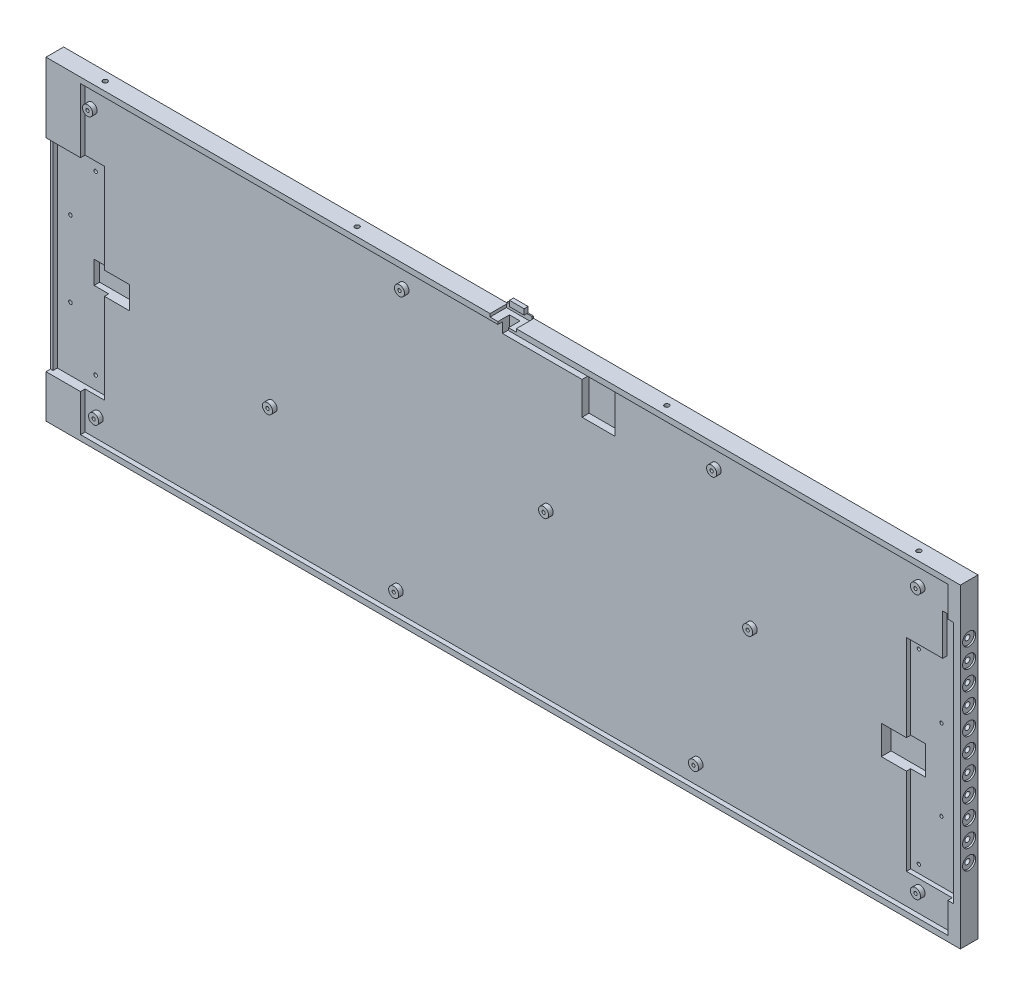
SolidWorks part; units mm, degrees
ref_plane "前视基准面" through (0, 0, 0) normal (0, 0, 1) x (1, 0, 0)
ref_plane "上视基准面" through (0, 0, 0) normal (0, 1, 0) x (1, 0, 0)
ref_plane "右视基准面" through (0, 0, 0) normal (1, 0, 0) x (0, 0, -1)
other "Configuration Table"
sketch "草图1" plane through (0, 0, 0) normal (0, 0, 1) x (1, 0, 0)
  line L1 (0, 0) -> (348.235, 0)
  line L2 (0, 0) -> (0, -124.714)
  line L3 (0, -124.714) -> (348.235, -124.714)
  line L4 (348.235, 0) -> (348.235, -124.714)
  dimension "D1" = 348.235
  dimension "D2" = 124.714
extrude "凸台-拉伸1" add sketch "草图1" along normal blind 7
sketch "草图2" plane through (0, 0, 7) normal (0, 0, 1) x (1, 0, 0)
  line L0 (348.235, 0) -> (0, 0) construction
  line L1 (2, -2) -> (346.235, -2)
  line L2 (2, -2) -> (2, -122.714)
  line L3 (2, -122.714) -> (346.235, -122.714)
  line L4 (346.235, -2) -> (346.235, -122.714)
  line L5 (348.235, -124.714) -> (348.235, 0) construction
  line L6 (0, -124.714) -> (348.235, -124.714) construction
  line L7 (0, 0) -> (0, -124.714) construction
  dimension "D1" = 2
  dimension "D2" = 2
  dimension "D3" = 2
  dimension "D4" = 2
extrude "切除-拉伸1" cut sketch "草图2" against normal blind 1.8
sketch "草图3" plane through (0, 0, 5.2) normal (0, 0, 1) x (1, 0, 0)
  circle A0 centre (4.8, -9.9) radius 2
  circle A1 centre (4.8, -9.9) radius 0.65
  circle A2 centre (7.2, -114.7) radius 2
  circle A3 centre (7.2, -114.7) radius 0.65
  circle A4 centre (76.2, -76.6) radius 2
  circle A5 centre (76.2, -76.6) radius 0.65
  circle A6 centre (128.6, -9.9) radius 2
  circle A7 centre (128.6, -9.9) radius 0.65
  circle A8 centre (126.3, -114.7) radius 2
  circle A9 centre (126.3, -114.7) radius 0.65
  circle A10 centre (185.8, -57.5) radius 2
  circle A11 centre (185.8, -57.5) radius 0.65
  circle A12 centre (252.5, -9.9) radius 2
  circle A13 centre (252.5, -9.9) radius 0.65
  circle A14 centre (245.3, -114.7) radius 2
  circle A15 centre (245.3, -114.7) radius 0.65
  circle A16 centre (333.4, -9.9) radius 2
  circle A17 centre (333.4, -9.9) radius 0.65
  circle A18 centre (333.4, -114.7) radius 2
  circle A19 centre (333.4, -114.7) radius 0.65
  circle A20 centre (266.8, -57.5) radius 2
  circle A21 centre (266.8, -57.5) radius 0.65
  dimension "D1" = 4
  dimension "D2" = 1.3
extrude "凸台-拉伸2" add sketch "草图3" along normal up to surface (1.8 mm away) up to face at (174.1175, -62.357, 7)
sketch "草图4" plane through (0, 0, 5.2) normal (0, 0, 1) x (1, 0, 0)
  line L0 (0, 0) -> (0, -124.714) construction
  line L1 (0, -27.514) -> (9.7, -27.514)
  line L2 (0, -27.514) -> (0, -107.914)
  line L3 (0, -107.914) -> (9.7, -107.914)
  line L4 (9.7, -27.514) -> (9.7, -107.914)
  line L5 (0, -124.714) -> (348.235, -124.714) construction
  dimension "D1" = 80.4
  dimension "D2" = 9.7
  dimension "D3" = 16.8
extrude "切除-拉伸2" cut sketch "草图4" against normal blind 1.7 and the other way through all contours L4 L3 L2 L1
sketch "草图6" plane through (0, 0, 5.2) normal (0, 0, 1) x (1, 0, 0)
  line L5 (3.9, -67.714) -> (9.7, -67.714) construction
  line L6 (3.9, -63.214) -> (19.7, -63.214)
  line L7 (3.9, -63.214) -> (3.9, -72.214)
  line L8 (3.9, -72.214) -> (19.7, -72.214)
  line L9 (19.7, -63.214) -> (19.7, -72.214)
  line L10 (9.7, -27.514) -> (9.7, -107.914) construction
  dimension "D1" = 9
  dimension "D2" = 5.8
  dimension "D3" = 10
extrude "切除-拉伸3" cut sketch "草图6" against normal offset from surface (3.9 mm away) 1.3 up to face at (174.1175, -62.357, 0)
sketch "草图7" plane through (0, 0, 0) normal (-1, 0, 0) x (0, 0, 1)
  line L1 (0, 0) -> (7, 0)
  line L2 (0, 0) -> (0, -27.514)
  line L3 (0, -27.514) -> (7, -27.514)
  line L4 (7, 0) -> (7, -27.514)
  line L5 (7, -107.914) -> (0, -107.914)
  line L6 (7, -107.914) -> (7, -124.714)
  line L7 (7, -124.714) -> (0, -124.714)
  line L8 (0, -107.914) -> (0, -124.714)
  line L9 (0, -107.914) -> (3.5, -107.914)
  line L10 (0, -107.914) -> (0, -27.514)
  line L11 (0, -27.514) -> (3.5, -27.514)
  line L12 (3.5, -107.914) -> (3.5, -27.514)
  line M1 (3.5, -107.914) -> (3.5, -27.514)
  line M2 (3.5, -27.514) -> (7, -27.514)
  line M3 (7, -27.514) -> (7, 0)
  line M4 (7, 0) -> (0, 0)
  line M5 (0, 0) -> (0, -124.714)
  line M6 (0, -124.714) -> (7, -124.714)
  line M7 (7, -124.714) -> (7, -107.914)
  line M8 (7, -107.914) -> (3.5, -107.914)
extrude "凸台-拉伸3" add sketch "草图7" along normal blind 11.7 contours L5 M8 M5 M6 M7 | L5 L3 M1 M5 | L3 M5 M2 M3 M4 region at (0, -13.757, 3.5) region at (0, -67.714, 1.75) region at (0, -116.314, 3.5)
sketch "草图8" plane through (0, 0, 3.5) normal (0, 0, 1) x (1, 0, 0)
  circle A0 centre (-5.5, -82.714) radius 0.7
  circle A1 centre (4.5, -102.714) radius 0.7
  circle A2 centre (-5.5, -52.714) radius 0.7
  circle A3 centre (4.5, -32.714) radius 0.7
  dimension "D1" = 1.4
extrude "切除-拉伸4" cut sketch "草图8" against normal blind 3
sketch "草图9" plane through (0, 0, 3.5) normal (0, 0, 1) x (1, 0, 0)
  line L0 (-11.7, -107.914) -> (2, -107.914) construction
  line L1 (-11.7, -27.514) -> (-10.7, -27.514)
  line L2 (-11.7, -27.514) -> (-11.7, -107.914)
  line L3 (-11.7, -107.914) -> (-10.7, -107.914)
  line L4 (-10.7, -27.514) -> (-10.7, -107.914)
  dimension "D1" = 1
extrude "凸台-拉伸4" add sketch "草图9" along normal up to surface (1.7 mm away) up to face at (64.8892, -65.9283, 5.2)
sketch "草图10" plane through (0, 0, 5.2) normal (0, 0, 1) x (1, 0, 0)
  line L1 (328.035, -30.314) -> (348.235, -30.314)
  line L2 (328.035, -30.314) -> (328.035, -110.714)
  line L3 (328.035, -110.714) -> (348.235, -110.714)
  line L4 (348.235, -30.314) -> (348.235, -110.714)
  line L6 (348.235, -124.714) -> (348.235, 0) construction
  line L9 (2, -122.714) -> (346.235, -122.714) construction
  dimension "D1" = 80.4
  dimension "D2" = 20.2
  dimension "D3" = 12
extrude "切除-拉伸5" cut sketch "草图10" against normal blind 1.7 and the other way through all
sketch "草图11" plane through (0, 0, 3.5) normal (0, 0, 1) x (1, 0, 0)
  line L0 (328.035, -70.514) -> (333.835, -70.514) construction
  line L1 (318.035, -64.764) -> (333.835, -64.764)
  line L2 (318.035, -64.764) -> (318.035, -76.264)
  line L3 (318.035, -76.264) -> (333.835, -76.264)
  line L4 (333.835, -64.764) -> (333.835, -76.264)
  line L5 (328.035, -110.714) -> (328.035, -30.314) construction
  dimension "D1" = 11.5
  dimension "D2" = 5.8
  dimension "D3" = 10
extrude "切除-拉伸6" cut sketch "草图11" against normal blind 2.2 and the other way through all
sketch "草图12" plane through (0, 0, 3.5) normal (0, 0, 1) x (1, 0, 0)
  circle A3 centre (331.235, -107.514) radius 0.65
  circle A4 centre (340.235, -86.514) radius 0.65
  circle A5 centre (340.235, -54.514) radius 0.65
  circle A6 centre (331.235, -33.514) radius 0.65
  dimension "D1" = 1.3
extrude "切除-拉伸7" cut sketch "草图12" against normal blind 3
sketch "草图13" plane through (0, 0, 0) normal (0, 0, -1) x (-1, 0, 0)
  line L0 (11.7, -124.714) -> (-348.235, -124.714) construction
  line L1 (-348.235, 0) -> (-351.235, 0)
  line L2 (-348.235, 0) -> (-348.235, -124.714)
  line L3 (-348.235, -124.714) -> (-351.235, -124.714)
  line L4 (-351.235, 0) -> (-351.235, -124.714)
  dimension "D1" = 3
extrude "凸台-拉伸5" add sketch "草图13" against normal up to surface (7 mm away) up to face at (171.1925, -14.957, 7)
sketch "草图14" plane through (0, 0, 5.2) normal (0, 0, 1) x (1, 0, 0)
  line L0 (346.235, -2) -> (2, -2) construction
  line L1 (342.435, -14) -> (348.435, -14)
  line L2 (342.435, -14) -> (342.435, -110.714)
  line L3 (342.435, -110.714) -> (348.435, -110.714)
  line L4 (348.435, -14) -> (348.435, -110.714)
  line L5 (346.235, -110.714) -> (328.035, -110.714) construction
  line L6 (351.235, 0) -> (351.235, -124.714) construction
  dimension "D1" = 12
  dimension "D2" = 6
  dimension "D3" = 2.8
extrude "切除-拉伸8" cut sketch "草图14" against normal up to surface (1.7 mm away) and the other way blind 3 up to face at (340.885, -86.514, 3.5)
sketch "草图15" plane through (351.235, 0, 0) normal (1, 0, 0) x (0, 0, -1)
  line L0 (-7, 0) -> (0, 0) construction
  line L1 (-3.5, -20) -> (-3.5, 0)
  line L2 (-3.5, -104.714) -> (-3.5, -124.714)
  line L4 (-7, -124.714) -> (0, -124.714) construction
  circle A0 centre (-3.5, -20) radius 2.6
  circle A12 centre (-3.5, -20) radius 1
  circle A13 centre (-3.5, -27.7013) radius 2.6
  circle A14 centre (-3.5, -27.7013) radius 1
  circle A15 centre (-3.5, -35.4025) radius 2.6
  circle A16 centre (-3.5, -35.4025) radius 1
  circle A17 centre (-3.5, -43.1038) radius 2.6
  circle A18 centre (-3.5, -43.1038) radius 1
  circle A19 centre (-3.5, -50.8051) radius 2.6
  circle A20 centre (-3.5, -50.8051) radius 1
  circle A21 centre (-3.5, -58.5064) radius 2.6
  circle A22 centre (-3.5, -58.5064) radius 1
  circle A23 centre (-3.5, -66.2076) radius 2.6
  circle A24 centre (-3.5, -66.2076) radius 1
  circle A25 centre (-3.5, -73.9089) radius 2.6
  circle A26 centre (-3.5, -73.9089) radius 1
  circle A27 centre (-3.5, -81.6102) radius 2.6
  circle A28 centre (-3.5, -81.6102) radius 1
  circle A29 centre (-3.5, -89.3115) radius 2.6
  circle A30 centre (-3.5, -89.3115) radius 1
  circle A31 centre (-3.5, -97.0127) radius 2.6
  circle A32 centre (-3.5, -97.0127) radius 1
  circle A33 centre (-3.5, -104.714) radius 2.6
  circle A34 centre (-3.5, -104.714) radius 1
  point P5 (-3.5, 0)
  dimension "D2" = 5.2
  dimension "D3" = 2
  dimension "D1" = 20
  dimension "D4" = 12
extrude "切除-拉伸9" cut sketch "草图15" against normal blind 0.7 contours A0 | A13 | A15 | A17 | A19 | A21 | A23 | A25 | A27 | A29 | A31
extrude "切除-拉伸10" cut sketch "草图15<3>" against normal up to surface (2.8 mm away) contours A12 | A14 | A16 | A18 | A20 | A22 | A24 | A26 | A28 | A30 | A32 up to face at (348.435, -62.357, 5.25)
sketch "草图15<3>" plane through (351.235, 0, 0) normal (1, 0, 0) x (0, 0, -1) same geometry as "草图15"
sketch "草图16" plane through (0, 0, 0) normal (0, 1, 0) x (1, 0, 0)
  line L1 (-11.7, 0) -> (351.235, 0)
  line L2 (-11.7, 0) -> (-11.7, -7)
  line L3 (-11.7, -7) -> (351.235, -7)
  line L4 (351.235, 0) -> (351.235, -7)
extrude "凸台-拉伸6" add sketch "草图16" along normal blind 0.2
sketch "草图17" plane through (0, -124.714, 0) normal (0, -1, 0) x (1, 0, 0)
  line L1 (-11.7, 7) -> (351.235, 7)
  line L2 (-11.7, 7) -> (-11.7, 0)
  line L3 (-11.7, 0) -> (351.235, 0)
  line L4 (351.235, 7) -> (351.235, 0)
extrude "凸台-拉伸7" add sketch "草图17" along normal blind 0.2
sketch "草图18" plane through (0, 0.2, 0) normal (0, 1, 0) x (1, 0, 0)
  line L0 (351.235, 0) -> (-11.7, 0) construction
  line L1 (164.5675, -0.5) -> (174.9675, -0.5)
  line L2 (164.5675, -0.5) -> (164.5675, -8.7)
  line L3 (164.5675, -8.7) -> (174.9675, -8.7)
  line L4 (174.9675, -0.5) -> (174.9675, -8.7)
  line L5 (164.5675, -0.5) -> (-11.7, -0.5) construction
  line L6 (-11.7, 0) -> (-11.7, -7) construction
  line L7 (174.9675, -0.5) -> (351.235, -0.5) construction
  line L8 (351.235, -7) -> (351.235, 0) construction
  dimension "D1" = 0.5
  dimension "D2" = 10.4
  dimension "D3" = 8.2
extrude "切除-拉伸11" cut sketch "草图18" against normal blind 1.2
sketch "草图19" plane through (0, 0.2, 0) normal (0, 1, 0) x (1, 0, 0)
  line L0 (174.9675, -7) -> (164.5675, -7) construction
  line L1 (167.6675, -2.4) -> (171.8675, -2.4)
  line L2 (167.6675, -2.4) -> (167.6675, -7)
  line L3 (167.6675, -7) -> (171.8675, -7)
  line L4 (171.8675, -2.4) -> (171.8675, -7)
  line L5 (169.7675, -2.4) -> (169.7675, 0) construction
  line L6 (351.235, 0) -> (-11.7, 0) construction
  line L7 (167.6675, -2.4) -> (-11.7, -2.4) construction
  line L8 (-11.7, 0) -> (-11.7, -7) construction
  line L9 (171.8675, -2.4) -> (351.235, -2.4) construction
  line L10 (351.235, -7) -> (351.235, 0) construction
  dimension "D1" = 2.4
  dimension "D2" = 4.2
extrude "切除-拉伸12" cut sketch "草图19" against normal up to surface (2.2 mm away) up to face at (174.1175, -2, 6.1)
sketch "草图20" plane through (0, 0.2, 0) normal (0, 1, 0) x (1, 0, 0)
  line L1 (174.7675, 0) -> (164.7675, 0)
  line L2 (174.7675, 0) -> (174.7675, -0.5)
  line L3 (174.7675, -0.5) -> (164.7675, -0.5)
  line L4 (164.7675, 0) -> (164.7675, -0.5)
  line L6 (351.235, 0) -> (-11.7, 0) construction
  point P15 (169.7675, 0)
  dimension "D1" = 10
  dimension "D2" = 0.5
extrude "凸台-拉伸8" add sketch "草图20" along normal blind 0.8
sketch "草图21" plane through (0, 1, 0) normal (0, 1, 0) x (1, 0, 0)
  line L0 (164.7675, 0) -> (174.7675, 0) construction
  line L1 (166.8675, 0) -> (172.6675, 0)
  line L2 (166.8675, 0) -> (166.8675, -1.6)
  line L3 (166.8675, -1.6) -> (172.6675, -1.6)
  line L4 (172.6675, 0) -> (172.6675, -1.6)
  point P6 (169.7675, 0)
  dimension "D1" = 5.8
  dimension "D2" = 1.6
extrude "凸台-拉伸9" add sketch "草图21" along normal blind 2.2
sketch "草图22" plane through (0, 0, 5.2) normal (0, 0, 1) x (1, 0, 0)
  line L1 (167.6675, -2) -> (212.2675, -2)
  line L2 (167.6675, -2) -> (167.6675, -6)
  line L3 (167.6675, -6) -> (212.2675, -6)
  line L4 (212.2675, -2) -> (212.2675, -6)
  line L5 (212.2675, -6) -> (199.2675, -6)
  line L6 (212.2675, -6) -> (212.2675, -19)
  line L7 (212.2675, -19) -> (199.2675, -19)
  line L8 (199.2675, -6) -> (199.2675, -19)
  line M20 (346.235, -2) -> (171.8675, -2)
  line M21 (171.8675, -2) -> (167.6675, -2)
  dimension "D1" = 4
  dimension "D2" = 44.6
  dimension "D3" = 13
  dimension "D4" = 13
extrude "切除-拉伸13" cut sketch "草图22" against normal up to surface (2.8 mm away) contours L4 L2 L3 M20 M21 | L3 L8 L7 L6 region at (189.9675, -4, 5.2) region at (205.7675, -12.5, 5.2) up to face at (169.7675, -1.5, 2.4)
sketch "草图23" plane through (0, 0, 0) normal (0, 0, -1) x (-1, 0, 0)
  line L0 (-351.235, 0.2) -> (-351.235, -124.914) construction
  line L1 (11.7, 0.2) -> (11.7, -124.914) construction
  line L2 (-351.235, 0.2) -> (-174.7675, 0.2) construction
  line L3 (11.7, -124.914) -> (-351.235, -124.914) construction
  circle A0 centre (-331.235, -19.8) radius 5.6
  circle A1 centre (-231.235, -19.8) radius 5.6
  circle A2 centre (-108.3, -19.8) radius 5.6
  circle A3 centre (-8.3, -19.8) radius 5.6
  circle A4 centre (-331.235, -104.914) radius 4.1
  circle A5 centre (-231.235, -104.914) radius 4.1
  circle A6 centre (-108.3, -104.914) radius 4.1
  circle A7 centre (-8.3, -104.914) radius 4.1
  dimension "D1" = 11.2
  dimension "D2" = 8.2
  dimension "D3" = 20
  dimension "D4" = 20
  dimension "D5" = 20
  dimension "D6" = 100
  dimension "D7" = 100
  dimension "D8" = 20
extrude "切除-拉伸14" cut sketch "草图23" against normal blind 1
sketch "草图24" plane through (0, 0.2, 0) normal (0, 1, 0) x (1, 0, 0)
  circle A0 centre (8.3, -3.5) radius 0.9
  circle A1 centre (108.3, -3.5) radius 0.9
  circle A2 centre (231.235, -3.5) radius 0.9
  circle A3 centre (331.235, -3.5) radius 0.9
  dimension "D1" = 1.8
sketch "草图25" plane through (0, 0, 5.2) normal (0, 0, 1) x (1, 0, 0)
  line L1 (-56.0241, 41.6365) -> (119.45, 41.6365)
  line L2 (-56.0241, 41.6365) -> (-56.0241, -143.708)
  line L3 (-56.0241, -143.708) -> (119.45, -143.708)
  line L4 (119.45, 41.6365) -> (119.45, -143.708)
extrude "切除-拉伸15" cut sketch "草图24" against normal blind 3
extrude "切除-拉伸16" cut sketch "草图24<2>" along normal blind 3 from surface starting at face at (169.7675, -124.914, 3.5)
sketch "草图24<2>" plane through (0, 0.2, 0) normal (0, 1, 0) x (1, 0, 0) same geometry as "草图24"
